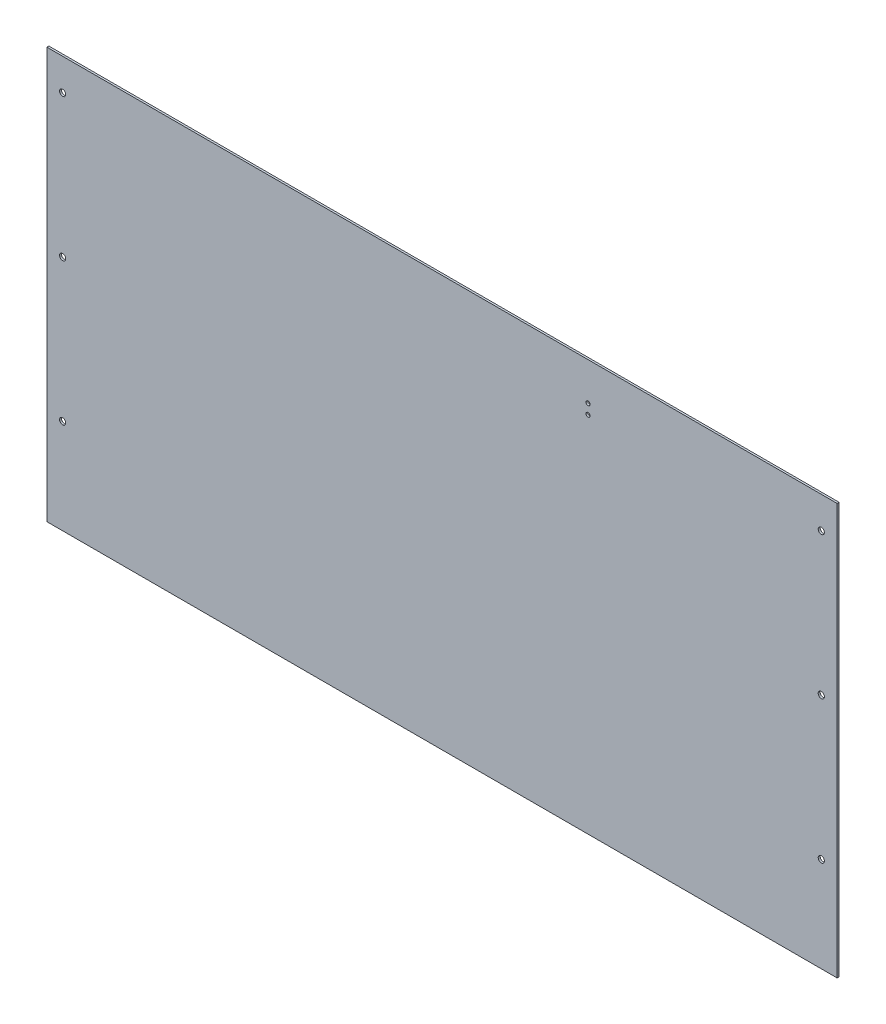
SolidWorks part; units mm, degrees
material "ABS PC"
ref_plane "Front Plane" through (0, 0, 0) normal (0, 0, 1) x (1, 0, 0)
ref_plane "Top Plane" through (0, 0, 0) normal (0, 1, 0) x (1, 0, 0)
ref_plane "Right Plane" through (0, 0, 0) normal (1, 0, 0) x (0, 0, -1)
sketch "Sketch1" plane through (0, 0, 0) normal (0, 0, 1) x (1, 0, 0)
  line L1 (-317.5, -165.1) -> (317.5, -165.1)
  line L2 (-317.5, -165.1) -> (-317.5, 165.1)
  line L3 (-317.5, 165.1) -> (317.5, 165.1)
  line L4 (317.5, -165.1) -> (317.5, 165.1)
  line L5 (0, 165.1) -> (0, -165.1) construction
  line L6 (-317.5, 0) -> (317.5, 0) construction
  point P0 (0, 0)
  point P4 (-222.25, 0)
  point P5 (222.25, 0)
  point P6 (0, 115.57)
  point P7 (0, -115.57)
  dimension "Length" = 635
  dimension "Width" = 330.2
  dimension "Break" = 95.25
  dimension "D2" = 95.25
  dimension "D1" = 49.53
  dimension "D3" = 49.53
sketch "Sketch2" plane through (0, 0, 0) normal (1, 0, 0) x (0, 0, -1)
  line L0 (-0.7937, -165.1) -> (0.7937, -165.1)
  dimension "Thickness" = 1.5875
sketch "Sketch3" plane through (0, 0, 0) normal (0, 0, 1) x (1, 0, 0)
  line L0 (-317.5, -165.1) -> (-317.5, 165.1) construction
  line L1 (-317.5, -165.1) -> (317.5, -165.1) construction
  line L2 (317.5, -165.1) -> (317.5, 165.1) construction
  line L3 (-317.5, 165.1) -> (317.5, 165.1) construction
  line L4 (-317.5, -165.1) -> (-317.5, 165.1)
  line L5 (-317.5, -165.1) -> (317.5, -165.1)
  line L6 (317.5, -165.1) -> (317.5, 165.1)
  line L7 (-317.5, 165.1) -> (317.5, 165.1)
extrude "Boss-Extrude1" add sketch "Sketch3" along normal mid plane 1.5875
sketch "Sketch4" plane through (0, 0, 0.7937) normal (0, 0, 1) x (1, 0, 0)
  line L0 (-317.5, 165.1) -> (-304.8, 165.1) construction
  line L1 (317.5, 165.1) -> (-317.5, 165.1) construction
  line L2 (-304.8, 165.1) -> (-304.8, 139.7) construction
  line L3 (-304.8, 139.7) -> (-304.8, 25.4) construction
  line L4 (-304.8, 25.4) -> (-304.8, -88.9) construction
  line L5 (317.5, 165.1) -> (304.8, 165.1) construction
  line L6 (304.8, 165.1) -> (304.8, 139.7) construction
  line L7 (304.8, 139.7) -> (304.8, 25.4) construction
  line L8 (304.8, 25.4) -> (304.8, -88.9) construction
  dimension "D1" = 25.4
  dimension "D2" = 114.3
  dimension "D3" = 114.3
hole_wizard "#10 Clearance Hole1" positions "Sketch5" profile "Sketch6" hole size "#10" standard "ANSI Inch" end condition through all
sketch "Sketch5" plane through (0, 0, 0.7937) normal (0, 0, 1) x (1, 0, 0)
  point P0 (-304.8, 139.7)
  point P4 (-304.8, 25.4)
  point P7 (-304.8, -88.9)
  point P10 (304.7359, 139.7)
  point P12 (304.7359, 25.4)
  point P14 (304.7359, -88.9)
sketch "Sketch6" plane through (-304.8, 139.7, 0.7937) normal (1, 0, 0) x (0, -1, 0)
  line L0 (0, 0) -> (0, 1.5875)
  line L1 (0, 1.5875) -> (2.4892, 1.5875)
  line L2 (2.4892, 1.5875) -> (2.4892, 0)
  line L5 (2.4892, 0) -> (0, 0)
  line L11 (0, -6.35) -> (0, 107.95) construction
  dimension "Thru Hole Dia." = 4.9784
  dimension "Thru Hole Depth" = 1.5875
sketch "Sketch7" plane through (0, 0, -0.7937) normal (0, 0, -1) x (-1, 0, 0)
  line L0 (-117.2884, 134.7) -> (-117.2884, 165.1) construction
  line L1 (-317.5, 165.1) -> (317.5, 165.1) construction
  line L2 (-117.2884, 134.7) -> (-292.0404, 134.7) construction
  line L3 (-292.0404, -276.662) -> (-292.0404, 333.2902) construction
  line L4 (-117.2884, 134.7) -> (-117.2884, 126.7) construction
  dimension "D1" = 30.4
  dimension "D2" = 174.752
hole_wizard "Ø3.2 (3.2) Diameter Hole1" positions "Sketch8" profile "Sketch9" hole size "Ø3.2" standard "ANSI Metric" end condition through all
sketch "Sketch8" plane through (0, 0, 0.7937) normal (0, 0, 1) x (1, 0, 0)
  point P0 (117.2884, 134.7)
  point P3 (117.2884, 126.7)
sketch "Sketch9" plane through (117.2884, 134.7, 0.7937) normal (1, 0, 0) x (0, -1, 0)
  line L0 (0, 0) -> (0, 1.5875)
  line L1 (0, 1.5875) -> (1.6, 1.5875)
  line L2 (1.6, 1.5875) -> (1.6, 0)
  line L5 (1.6, 0) -> (0, 0)
  line L11 (0, -6.35) -> (0, 107.95) construction
  dimension "Thru Hole Dia." = 3.2
  dimension "Thru Hole Depth" = 1.5875
equation "\"D1@Boss-Extrude1\"=\"thickness@sketch2\""
equation "\"Break@Sketch1\" = \"Length@Sketch1\" * 0.15"
equation "\"D2@Sketch1\" = \"Break@Sketch1\""
equation "\"D1@Sketch1\"=\"Width@Sketch1\"*0.15"
equation "\"D3@Sketch1\"=\"D1@Sketch1\""
